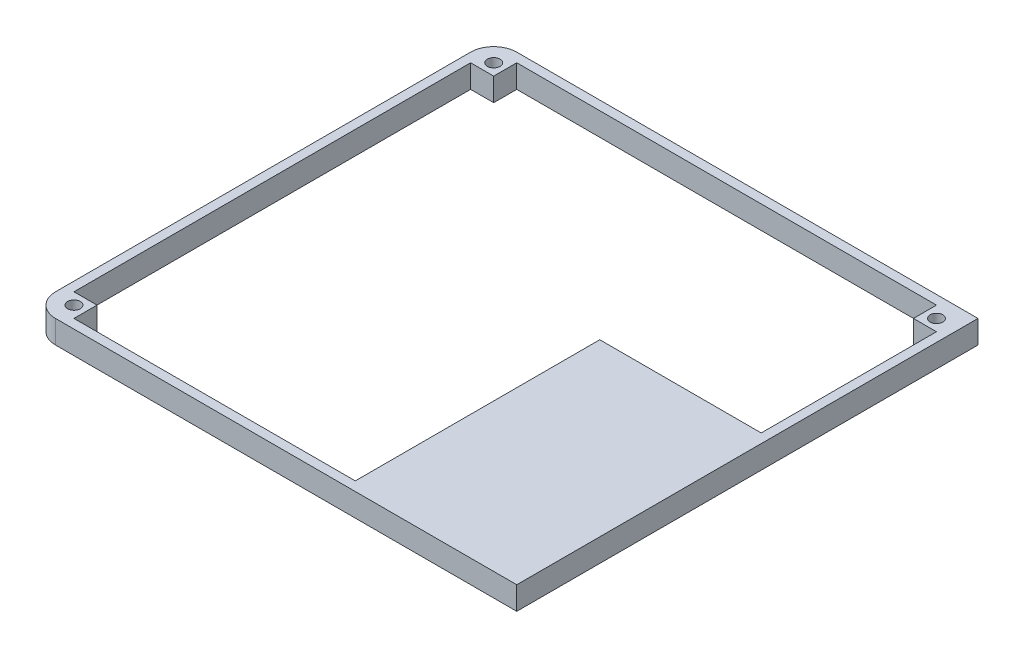
SolidWorks part; units mm, degrees
ref_plane "Front Plane" through (0, 0, 0) normal (0, 0, 1) x (1, 0, 0)
ref_plane "Top Plane" through (0, 0, 0) normal (0, 1, 0) x (1, 0, 0)
ref_plane "Right Plane" through (0, 0, 0) normal (1, 0, 0) x (0, 0, -1)
sketch "Sketch1" plane through (0, 0, 0) normal (0, 1, 0) x (1, 0, 0)
  line L1 (0, 0) -> (210, 0)
  line L2 (0, 0) -> (0, 200)
  line L3 (0, 200) -> (210, 200)
  line L4 (210, 0) -> (210, 200)
  line L5 (4, 196) -> (206, 196)
  line L6 (4, 196) -> (4, 4)
  line L7 (4, 4) -> (206, 4)
  line L8 (206, 196) -> (206, 4)
  dimension "D1" = 210
  dimension "D2" = 200
  dimension "D3" = 202
  dimension "D4" = 192
  dimension "D5" = 4
  dimension "D6" = 4
extrude "Boss-Extrude1" add sketch "Sketch1" against normal blind 10
sketch "Sketch2" plane through (0, -10, 0) normal (0, -1, 0) x (1, 0, 0)
  line L1 (210, 0) -> (140, 0)
  line L2 (210, 0) -> (210, -106)
  line L3 (210, -106) -> (140, -106)
  line L4 (140, 0) -> (140, -106)
  dimension "D1" = 70
  dimension "D2" = 106
extrude "Boss-Extrude2" add sketch "Sketch2" against normal blind 10
sketch "Sketch3" plane through (0, -10, 0) normal (0, -1, 0) x (1, 0, 0)
  line L5 (140, -4) -> (206, -4)
  line L6 (140, -4) -> (140, -106)
  line L7 (140, -106) -> (206, -106)
  line L8 (206, -4) -> (206, -106)
extrude "Cut-Extrude1" cut sketch "Sketch3" against normal blind 5
sketch "Sketch4" plane through (0, -10, 0) normal (0, -1, 0) x (1, 0, 0)
  line L1 (4, -4) -> (14, -4)
  line L2 (4, -4) -> (4, -14)
  line L3 (4, -14) -> (14, -14)
  line L4 (14, -4) -> (14, -14)
  line L5 (4, -196) -> (14, -196)
  line L6 (4, -196) -> (4, -186)
  line L7 (4, -186) -> (14, -186)
  line L8 (14, -196) -> (14, -186)
  line L9 (206, -196) -> (196, -196)
  line L10 (206, -196) -> (206, -186)
  line L11 (206, -186) -> (196, -186)
  line L12 (196, -196) -> (196, -186)
  circle A0 centre (9, -9) radius 2.75
  circle A1 centre (9, -191) radius 2.75
  circle A2 centre (201, -191) radius 2.75
  dimension "D1" = 10
  dimension "D2" = 10
  dimension "D3" = 10
  dimension "D4" = 10
  dimension "D5" = 10
  dimension "D6" = 10
extrude "Boss-Extrude3" add sketch "Sketch4" against normal blind 10
fillet "Fillet1" radius 10 2 edges at (0, -5, 0) (0, -5, -200)
sketch "Sketch5" plane through (0, -5, 0) normal (0, -1, 0) x (1, 0, 0)
  line L0 (140, -4) -> (140, -106) construction
  line L2 (206, -4) -> (206, -110)
  line L3 (206, -110) -> (136, -110)
  line L4 (136, -4) -> (136, -110)
  line L5 (140, -106) -> (206, -106) construction
  line L6 (136, -4) -> (140, -4)
  line L7 (140, -4) -> (140, -106)
  line L8 (140, -106) -> (206, -106)
  line L9 (206, -106) -> (206, -110)
  line M5 (140, -106) -> (206, -106)
  line M8 (140, -4) -> (140, -106)
  dimension "D1" = 4
  dimension "D2" = 4
extrude "Boss-Extrude4" add sketch "Sketch5" along normal blind 5 and the other way blind 5 contours L6 L4 L3 L2 M5 M8 region at (204.7297, -5, -108)
